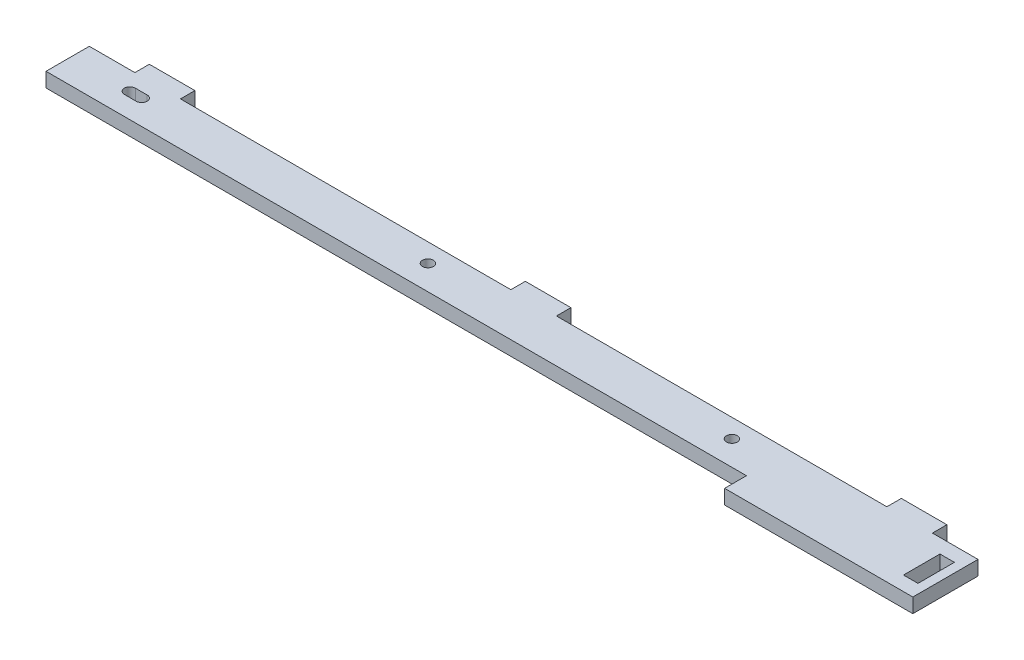
SolidWorks part; units mm, degrees
material "Acrylic (Medium-high impact)"
ref_plane "Front Plane" through (0, 0, 0) normal (0, 0, 1) x (1, 0, 0)
ref_plane "Top Plane" through (0, 0, 0) normal (0, 1, 0) x (1, 0, 0)
ref_plane "Right Plane" through (0, 0, 0) normal (1, 0, 0) x (0, 0, -1)
sketch "Sketch1" plane through (0, 0, 0) normal (0, 1, 0) x (1, 0, 0)
  line L1 (97.5, -4.75) -> (-97.5, -4.75)
  line L2 (97.5, -4.75) -> (97.5, 4.75)
  line L3 (97.5, 4.75) -> (-97.5, 4.75)
  line L4 (-97.5, -4.75) -> (-97.5, 4.75)
  line L5 (97.5, -4.75) -> (-97.5, 4.75) construction
  line L6 (97.5, 4.75) -> (-97.5, -4.75) construction
  point P0 (0, 0)
  dimension "D1" = 9.5
  dimension "D2" = 195
extrude "Boss-Extrude1" add sketch "Sketch1" along normal blind 3.175
hole_wizard "M2 Clearance Hole1" positions "Sketch4" profile "Sketch3" hole size "M2" standard "ANSI Metric" end condition through all
sketch "Sketch4" plane through (0, 3.175, 0) normal (0, 1, 0) x (1, 0, 0)
  line L0 (-83.2, 0.65) -> (47.6, 0.65) construction
  line L2 (-97.5, -4.75) -> (97.5, -4.75) construction
  line L4 (-97.5, 4.75) -> (-97.5, -4.75) construction
  point P0 (-83.2, 0.65)
  point P4 (47.6, 0.65)
  point P11 (-19.1, 0.65)
  dimension "D1" = 5.4
  dimension "D2" = 66.7
  dimension "D3" = 64.1
  dimension "D4" = 14.3
sketch "Sketch3" plane through (-83.2, 3.175, -0.65) normal (1, 0, 0) x (0, 0, 1)
  line L0 (0, 0) -> (0, 3.175)
  line L1 (0, 3.175) -> (1.2, 3.175)
  line L2 (1.2, 3.175) -> (1.2, 0)
  line L5 (1.2, 0) -> (0, 0)
  line L11 (0, -6.35) -> (0, 107.95) construction
  dimension "Thru Hole Dia." = 2.4
  dimension "Thru Hole Depth" = 3.175
sketch "Sketch5" plane through (0, 0, -4.75) normal (0, 0, -1) x (-1, 0, 0)
  line L0 (-97.5, 0) -> (97.5, 0) construction
  line L1 (87.5, 0) -> (77.5, 0)
  line L2 (87.5, 0) -> (87.5, 3.175)
  line L3 (87.5, 3.175) -> (77.5, 3.175)
  line L4 (77.5, 0) -> (77.5, 3.175)
  line L5 (-97.5, 3.175) -> (97.5, 3.175) construction
  line L6 (97.5, 3.175) -> (97.5, 0) construction
  line L7 (0, 1.7463) -> (0, -1.7463) construction
  line L8 (-87.5, 3.175) -> (-77.5, 3.175)
  line L9 (-77.5, 0) -> (-77.5, 3.175)
  line L10 (-87.5, 0) -> (-77.5, 0)
  line L11 (-87.5, 0) -> (-87.5, 3.175)
  line L13 (5, 0) -> (-5, 0)
  line L14 (5, 0) -> (5, 3.175)
  line L15 (5, 3.175) -> (-5, 3.175)
  line L16 (-5, 0) -> (-5, 3.175)
  dimension "D1" = 10
  dimension "D2" = 10
extrude "Boss-Extrude2" add sketch "Sketch5" along normal blind 3.175
sketch "Sketch6" plane through (0, 0, 4.75) normal (0, 0, 1) x (1, 0, 0)
  line L0 (-97.5, 3.175) -> (97.5, 3.175) construction
  line L1 (56.2, 3.175) -> (97.5, 3.175)
  line L2 (56.2, 3.175) -> (56.2, 0)
  line L3 (56.2, 0) -> (97.5, 0)
  line L4 (97.5, 3.175) -> (97.5, 0)
  line L5 (48.8, 3.175) -> (46.4, 3.175) construction
  line L6 (48.8, 3.175) -> (46.4, 3.175) construction
  line L7 (47.6, 3.175) -> (47.6, 0) construction
  line L8 (-97.5, 0) -> (97.5, 0) construction
  dimension "D1" = 8.6
extrude "Boss-Extrude3" add sketch "Sketch6" along normal blind 4.8
sketch "Sketch7" plane through (0, 0, 0) normal (0, -1, 0) x (1, 0, 0)
  line L1 (92.3, -1.6) -> (95.475, -1.6)
  line L2 (92.3, -1.6) -> (92.3, 6.4)
  line L3 (92.3, 6.4) -> (95.475, 6.4)
  line L4 (95.475, -1.6) -> (95.475, 6.4)
extrude "Cut-Extrude1" cut sketch "Sketch7" against normal through all
hole_wizard "M2 Clearance Slot1" positions "Sketch8" profile "Sketch9" size "M2" standard "ANSI Metric" slot yes end condition through all
sketch "Sketch8" plane through (0, 0, 0) normal (0, -1, 0) x (-1, 0, 0)
  line L0 (85.7, 0.65) -> (80.7, 0.65) construction
  point P0 (83.2, 0.65)
  dimension "D1" = 5
sketch "Sketch9" plane through (-83.2, 0, -0.65) normal (1, 0, 0) x (0, 0, -1)
  line L0 (0, 0) -> (0, 3.175)
  line L1 (0, 3.175) -> (1.2, 3.175)
  line L2 (1.2, 3.175) -> (1.2, 0)
  line L5 (1.2, 0) -> (0, 0)
  line L11 (0, -6.35) -> (0, 107.95) construction
  dimension "Thru Hole Dia." = 2.4
  dimension "Thru Hole Depth" = 3.175
